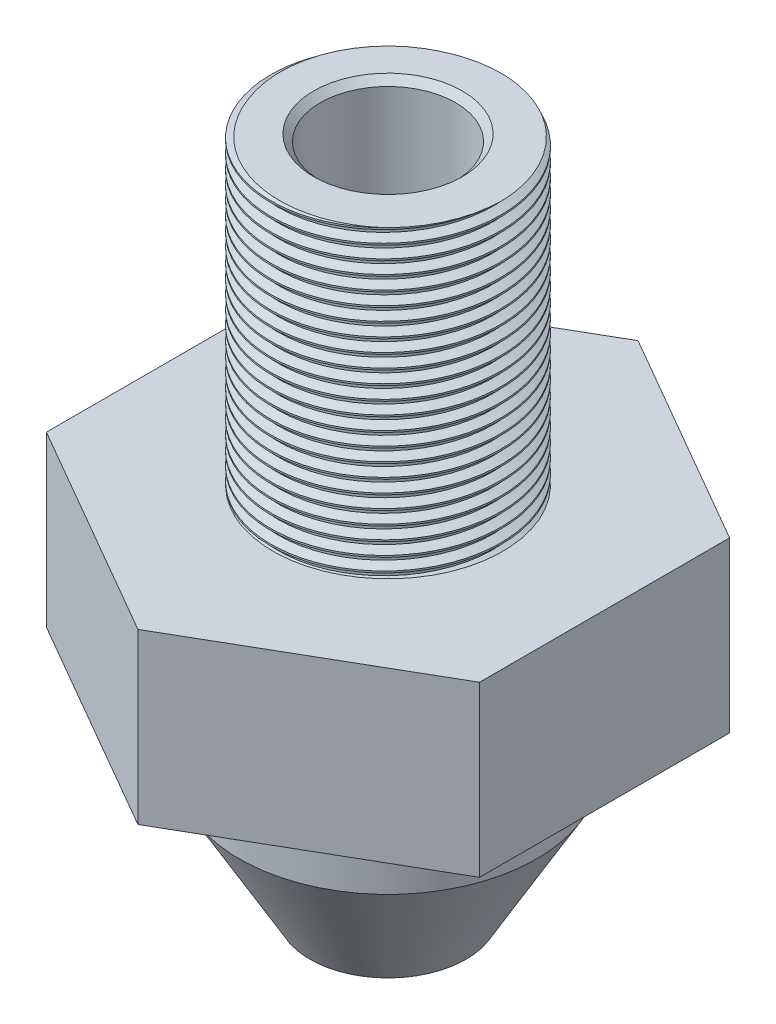
SolidWorks part; units mm, degrees
ref_plane "Front Plane" through (0, 0, 0) normal (0, 0, 1) x (1, 0, 0)
ref_plane "Top Plane" through (0, 0, 0) normal (0, 1, 0) x (1, 0, 0)
ref_plane "Right Plane" through (0, 0, 0) normal (1, 0, 0) x (0, 0, -1)
sketch "Sketch1" plane through (0, 0, 0) normal (0, 0, 1) x (1, 0, 0)
  line L0 (0, 0) -> (0, 124.3593) construction
  line L1 (-25.4, 254) -> (-25.4, 25.4)
  line L2 (-25.4, 25.4) -> (-10.7353, 0)
  line L3 (-10.7353, 0) -> (-29.3516, 0)
  line L4 (-29.3516, 0) -> (-55.88, 45.9485)
  line L5 (-55.88, 45.9485) -> (-55.88, 76.2)
  line L6 (-55.88, 76.2) -> (-93.98, 76.2)
  line L7 (-93.98, 76.2) -> (-93.98, 139.7)
  line L8 (-93.98, 139.7) -> (-43.18, 139.7)
  line L9 (-43.18, 139.7) -> (-43.18, 254)
  line L10 (-43.18, 254) -> (-25.4, 254)
  point P13 (-20.0435, 0)
  point P14 (-60.9501, 44.572)
  dimension "D1" = 43.18
  dimension "D2" = 150
  dimension "D3" = 254
  dimension "D4" = 228.6
  dimension "D5" = 50.8
  dimension "D6" = 63.5
  dimension "D7" = 114.3
  dimension "D8" = 38.1
  dimension "D9" = 25.4
  dimension "D10" = 150
revolve "Revolve1" add sketch "Sketch1" angle 360 about L0
thread "Thread1" pitch 5.08 start angle 0, offset 12.7, length 0, pitch 5.08, diameter 86.36
ref_plane "Plane1" through (-43.18, 266.7, 0) normal (0, 0, 1) x (-1, 0, 0)
sketch "Thread Profile1" plane through (-43.18, 266.7, 0) normal (0, 0, 1) x (-1, 0, 0)
  line L0 (0, 0) -> (0, 5.08) construction
  line L11 (0, 0) -> (0, 4.445)
  line L12 (0, 4.445) -> (-2.7496, 2.8575)
  line L13 (-2.7496, 2.8575) -> (-2.7496, 1.5875)
  line L15 (-2.7496, 1.5875) -> (0, 0)
  line L17 (-2.7496, 2.2225) -> (0, 2.2225) construction
  point P2 (0, 0)
  dimension "Pitch" = 5.08
  dimension "Profile_Angle" = 60
  dimension "Profile_Land" = 1.27
  dimension "Profile_Height" = 2.7496
chamfer "Chamfer1" distance 12.7 angle 45 1 edges at (0, 76.2, -55.88)
sketch "Sketch20" plane through (0, 76.2, 0) normal (0, -1, 0) x (1, 0, 0)
  line L1 (0, 93.98) -> (-81.3891, 46.99)
  line L2 (-81.3891, 46.99) -> (-81.3891, -46.99)
  line L3 (-81.3891, -46.99) -> (0, -93.98)
  line L4 (0, -93.98) -> (81.3891, -46.99)
  line L5 (81.3891, -46.99) -> (81.3891, 46.99)
  line L6 (81.3891, 46.99) -> (0, 93.98)
  circle A0 centre (0, 0) radius 81.3891 construction
extrude "Cut-Extrude1" cut sketch "Sketch20" against normal through all flip side to cut
chamfer "Chamfer2" distance 2.54 angle 45 2 edges at (0, 0, -10.7353) (0, 254, -25.4)
